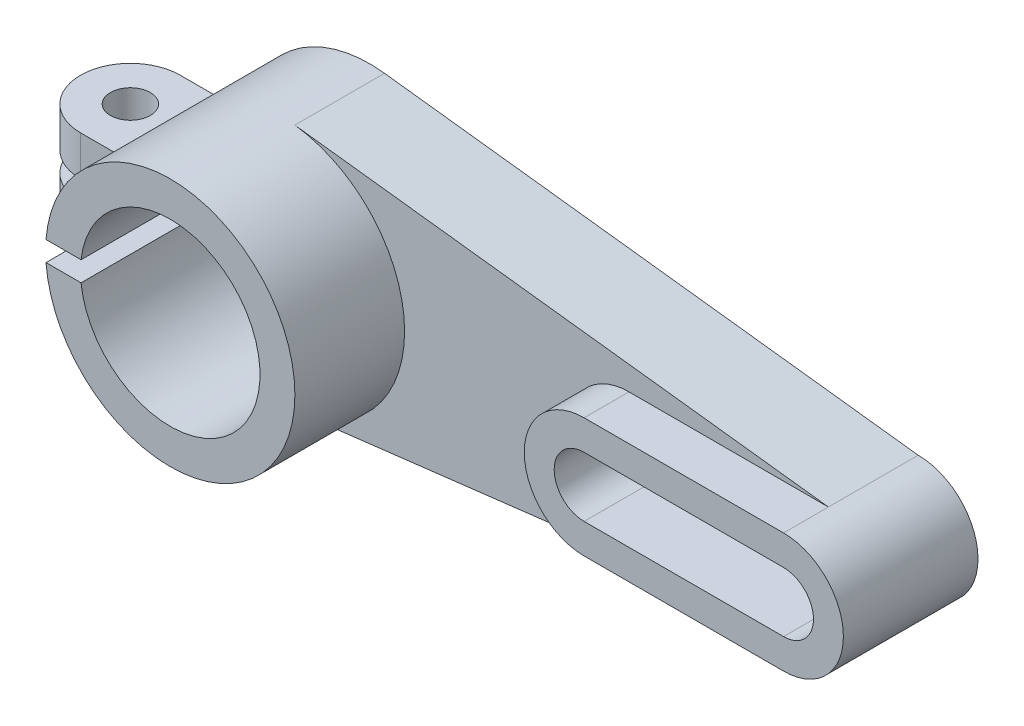
SolidWorks part; units mm, degrees
ref_plane "Front Plane" through (0, 0, 0) normal (0, 0, 1) x (1, 0, 0)
ref_plane "Top Plane" through (0, 0, 0) normal (0, 1, 0) x (1, 0, 0)
ref_plane "Right Plane" through (0, 0, 0) normal (1, 0, 0) x (0, 0, -1)
sketch "Sketch1" plane through (0, 0, 0) normal (0, 0, 1) x (1, 0, 0)
  line L0 (-34.0417, 0) -> (156.3369, 0) construction
  line L1 (0, 32.0171) -> (0, -32.6667) construction
  line L2 (110, 12) -> (2.9739, 24.8225)
  line L3 (110, -12) -> (2.9739, -24.8225)
  arc A0 (110, -12) -> (110, 12) centre (110, 0) ccw
  arc A1 (2.9739, 24.8225) -> (2.9739, -24.8225) centre (0, 0) ccw
  point P6 (0, 0)
  point P12 (0, 32.0171)
  point P13 (0, 0)
  point P14 (-18.5913, -24.0412)
  point P15 (-20.1021, 23.9074)
  point P16 (0, -32.6667)
  point P17 (0, 0)
  point P18 (0, 0)
  point P19 (156.3369, 0)
  point P20 (-34.0417, 0)
  dimension "D1" = 24
  dimension "D2" = 50
  dimension "D3" = 110
extrude "Boss-Extrude1" add sketch "Sketch1" against normal blind 18
ref_plane "Plane1" through (0, 0, 9) normal (0, 0, 1) x (1, 0, 0)
sketch "Sketch2" plane through (0, 0, 9) normal (0, 0, 1) x (1, 0, 0)
  line L0 (-55.0331, 0) -> (149.1616, 0) construction
  line L1 (0, 54.638) -> (0, -57.5095) construction
  line L2 (110, 0) -> (70, 0) construction
  line L3 (110, -12) -> (70, -12)
  line L4 (110, 12) -> (70, 12)
  line L5 (70, 0) -> (110, 0) construction
  line L6 (70, 6) -> (110, 6)
  line L7 (70, -6) -> (110, -6)
  arc A0 (110, -12) -> (110, 12) centre (110, 0) ccw
  arc A1 (70, 12) -> (70, -12) centre (70, 0) ccw
  arc A2 (70, 6) -> (70, -6) centre (70, 0) ccw
  arc A3 (110, -6) -> (110, 6) centre (110, 0) ccw
  arc A4 (110, -12) -> (110, 12) centre (110, 0) ccw construction
  point P7 (90, 0)
  point P14 (90, 0)
  point P22 (0, 0)
  point P23 (63.1765, 6)
  dimension "D1" = 12
  dimension "D2" = 12
  dimension "D3" = 40
extrude "Boss-Extrude2" add sketch "Sketch2" against normal blind 9
extrude "Cut-Extrude1" cut sketch "Sketch2<2>" against normal through all contours L7 A3 L6 A2 region at (90, 0, 9)
sketch "Sketch2<2>" plane through (0, 0, 9) normal (0, 0, 1) x (1, 0, 0) same geometry as "Sketch2"
ref_plane "Plane2" through (0, 0, 22) normal (0, 0, 1) x (1, 0, 0)
sketch "Sketch3" plane through (0, 0, 22) normal (0, 0, 1) x (1, 0, 0)
  line L0 (-61.1749, 0) -> (158.3504, 0) construction
  line L1 (0, 51.8543) -> (0, -50.275) construction
  circle A0 centre (0, 0) radius 25
  arc A1 (2.9739, 24.8225) -> (2.9739, -24.8225) centre (0, 0) ccw construction
  circle A2 centre (0, 0) radius 18
  dimension "D1" = 50
  dimension "D2" = 36
extrude "Boss-Extrude3" add sketch "Sketch3" against normal up to surface (22 mm away) up to face at (54.329, 0, 0)
extrude "Cut-Extrude2" cut sketch "Sketch3<2>" against normal through all contours A2 region at (0, 0, 22)
sketch "Sketch3<2>" plane through (0, 0, 22) normal (0, 0, 1) x (1, 0, 0) same geometry as "Sketch3"
sketch "Sketch6" plane through (0, 0, 0) normal (0, 1, 0) x (1, 0, 0)
  line L0 (-52.9592, 0) -> (152.8307, 0) construction
  line L1 (0, 44.3426) -> (0, -41.3234) construction
  line L2 (-19, 12) -> (-32, 12)
  line L3 (-25, -22) -> (25, -22) construction
  line L4 (-19, -8) -> (-32, -8)
  line L5 (-32, 12) -> (-32, -8) construction
  line L6 (-19, 12) -> (-19, -8)
  arc A0 (-32, 12) -> (-32, -8) centre (-32, 2) ccw
  circle A1 centre (-32, 2) radius 4
  point P12 (0, 0)
  point P15 (0, 0)
  point P16 (-33.3244, -8)
  point P17 (0, 0)
  point P18 (0, 0)
  dimension "D1" = 8
  dimension "D4" = 10
  dimension "D2" = 20
  dimension "D3" = 14
  dimension "D5" = 32
  dimension "D6" = 13
extrude "Boss-Extrude5" add sketch "Sketch6" along normal mid plane 20
ref_plane "Plane4" through (-42, 0, 0) normal (1, 0, 0) x (0, 0, -1)
sketch "Sketch7" plane through (-42, 0, 0) normal (1, 0, 0) x (0, 0, -1)
  line L0 (40.0197, 0) -> (-32.0471, 0) construction
  line L1 (0, 30.0858) -> (0, -31.5534) construction
  line L3 (30.0554, -2) -> (-27.0264, -2)
  line L4 (30.0554, -2) -> (30.0554, 2)
  line L5 (30.0554, 2) -> (-27.0264, 2)
  line L6 (-27.0264, -2) -> (-27.0264, 2)
  dimension "D1" = 4
  dimension "D2" = 30.0554
  dimension "D3" = 27.0264
extrude "Cut-Extrude3" cut sketch "Sketch7" along normal blind 40
